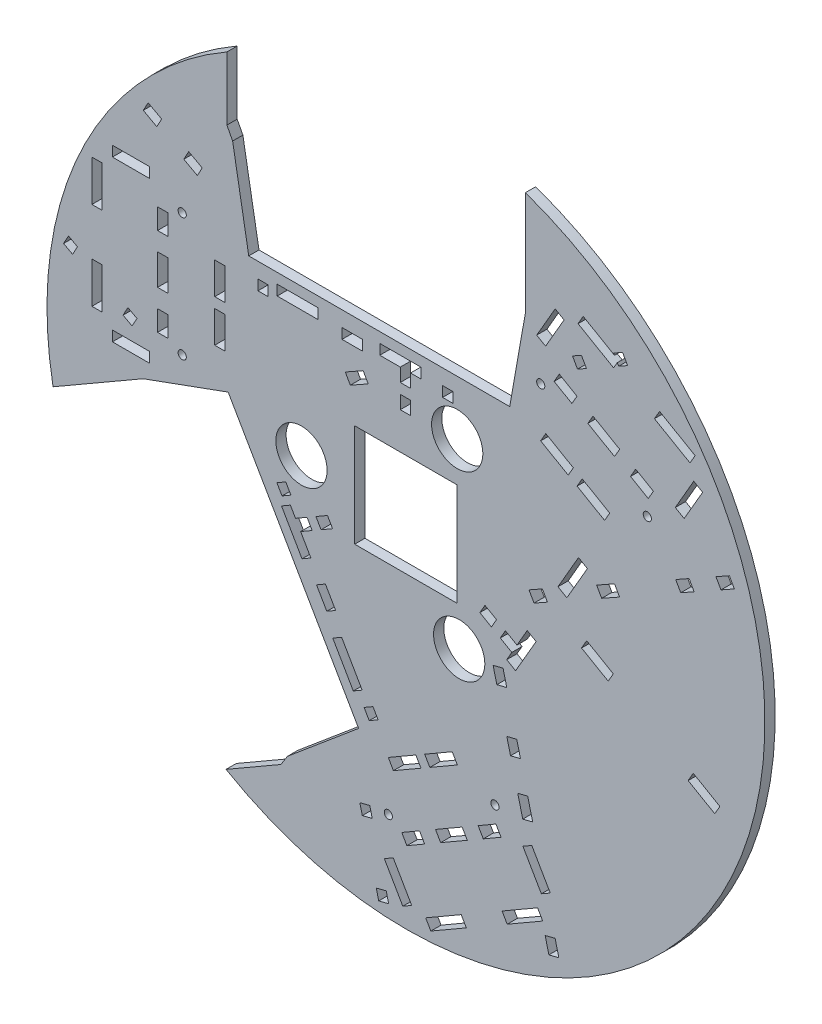
SolidWorks part; units mm, degrees
material "Balsa"
ref_plane "Plan de face" through (0, 0, 0) normal (0, 0, 1) x (1, 0, 0)
ref_plane "Plan de dessus" through (0, 0, 0) normal (0, 1, 0) x (1, 0, 0)
ref_plane "Plan de droite" through (0, 0, 0) normal (1, 0, 0) x (0, 0, -1)
sketch "Esquisse1" plane through (0, 0, 0) normal (0, 0, 1) x (1, 0, 0)
  circle A0 centre (148.0804, -12.1102) radius 175
  dimension "D1" = 350
extrude "Boss.-Extru.1" add sketch "Esquisse1" along normal blind 5
sketch "Esquisse2" plane through (0, 0, 5) normal (0, 0, 1) x (1, 0, 0)
  line L0 (135.3118, 53.7774) -> (135.3118, 48.7774)
  line L1 (5, 72.2774) -> (23, 72.2774)
  line L2 (5, 72.2774) -> (5, 67.2774)
  line L3 (5, 67.2774) -> (23, 67.2774)
  line L4 (23, 72.2774) -> (23, 67.2774)
  line L5 (-5, 62.2774) -> (0, 62.2774)
  line L6 (-5, 62.2774) -> (-5, 42.2774)
  line L7 (-5, 42.2774) -> (0, 42.2774)
  line L8 (0, 62.2774) -> (0, 42.2774)
  line L9 (-5, 19.2774) -> (0, 19.2774)
  line L10 (-5, 19.2774) -> (-5, -0.7226)
  line L11 (-5, -0.7226) -> (0, -0.7226)
  line L12 (0, 19.2774) -> (0, -0.7226)
  line L13 (5, -5.7226) -> (23, -5.7226)
  line L14 (5, -5.7226) -> (5, -10.7226)
  line L15 (5, -10.7226) -> (23, -10.7226)
  line L16 (23, -5.7226) -> (23, -10.7226)
  line L17 (27, 14.2774) -> (32, 14.2774)
  line L18 (27, 14.2774) -> (27, 4.2774)
  line L19 (27, 4.2774) -> (32, 4.2774)
  line L20 (32, 14.2774) -> (32, 4.2774)
  line L21 (27, 38.2774) -> (32, 38.2774)
  line L22 (27, 38.2774) -> (27, 23.2774)
  line L23 (27, 23.2774) -> (32, 23.2774)
  line L24 (32, 38.2774) -> (32, 23.2774)
  line L25 (27, 57.2774) -> (32, 57.2774)
  line L26 (27, 57.2774) -> (27, 47.2774)
  line L27 (27, 47.2774) -> (32, 47.2774)
  line L28 (32, 57.2774) -> (32, 47.2774)
  line L29 (54.86, 48.7774) -> (59.86, 48.7774)
  line L30 (54.86, 48.7774) -> (54.86, 33.2774)
  line L31 (54.86, 33.2774) -> (59.86, 33.2774)
  line L32 (59.86, 48.7774) -> (59.86, 33.2774)
  line L33 (54.86, 28.2774) -> (59.86, 28.2774)
  line L34 (54.86, 28.2774) -> (54.86, 12.7774)
  line L35 (54.86, 12.7774) -> (59.86, 12.7774)
  line L36 (59.86, 28.2774) -> (59.86, 12.7774)
  line L37 (85.3118, 53.7774) -> (105.3118, 53.7774)
  line L38 (85.3118, 53.7774) -> (85.3118, 48.7774)
  line L39 (85.3118, 48.7774) -> (105.3118, 48.7774)
  line L40 (105.3118, 53.7774) -> (105.3118, 48.7774)
  line L41 (145.3118, 37.2774) -> (150.3118, 37.2774)
  line L42 (145.3118, 37.2774) -> (145.3118, 30.7774)
  line L43 (145.3118, 30.7774) -> (150.3118, 30.7774)
  line L44 (150.3118, 37.2774) -> (150.3118, 30.7774)
  line L45 (135.3118, 48.7774) -> (145.3118, 48.7774)
  line L46 (155.3118, 48.7774) -> (135.3118, 48.7774) construction
  line L47 (145.3118, 48.7774) -> (145.3118, 42.2774)
  line L48 (145.3118, 42.2774) -> (150.3118, 42.2774)
  line L49 (150.3118, 42.2774) -> (150.3118, 48.7774)
  line L50 (150.3118, 48.7774) -> (155.3118, 48.7774)
  line L51 (155.3118, 48.7774) -> (155.3118, 53.7774)
  line L52 (155.3118, 53.7774) -> (135.3118, 53.7774)
  line L53 (292.7025, 69.6073) -> (283.7025, 54.0188)
  line L54 (292.7025, 69.6073) -> (288.3723, 72.1073)
  line L55 (288.3723, 72.1073) -> (279.3723, 56.5188)
  line L56 (283.7025, 54.0188) -> (279.3723, 56.5188)
  line L57 (289.0422, 83.2676) -> (286.5422, 78.9374)
  line L58 (289.0422, 83.2676) -> (271.7217, 93.2676)
  line L59 (271.7217, 93.2676) -> (269.2217, 88.9374)
  line L60 (286.5422, 78.9374) -> (269.2217, 88.9374)
  line L61 (251.8031, 104.7676) -> (249.3031, 100.4374)
  line L62 (251.8031, 104.7676) -> (234.4826, 114.7676)
  line L63 (234.4826, 114.7676) -> (231.9826, 110.4374)
  line L64 (249.3031, 100.4374) -> (231.9826, 110.4374)
  line L65 (225.1525, 108.6073) -> (216.1525, 93.0188)
  line L66 (225.1525, 108.6073) -> (220.8223, 111.1073)
  line L67 (220.8223, 111.1073) -> (211.8223, 95.5188)
  line L68 (216.1525, 93.0188) -> (211.8223, 95.5188)
  line L69 (231.473, 79.5547) -> (228.973, 75.2246)
  line L70 (231.473, 79.5547) -> (222.8127, 84.5547)
  line L71 (222.8127, 84.5547) -> (220.3127, 80.2246)
  line L72 (228.973, 75.2246) -> (220.3127, 80.2246)
  line L73 (252.2576, 67.5547) -> (249.7576, 63.2246)
  line L74 (252.2576, 67.5547) -> (239.2672, 75.0547)
  line L75 (239.2672, 75.0547) -> (236.7672, 70.7246)
  line L76 (249.7576, 63.2246) -> (236.7672, 70.7246)
  line L77 (268.7121, 58.0547) -> (266.2121, 53.7246)
  line L78 (268.7121, 58.0547) -> (260.0518, 63.0547)
  line L79 (260.0518, 63.0547) -> (257.5518, 58.7246)
  line L80 (266.2121, 53.7246) -> (257.5518, 58.7246)
  line L81 (247.4209, 38.1773) -> (244.9209, 33.8472)
  line L82 (247.4209, 38.1773) -> (233.9975, 45.9273)
  line L83 (233.9975, 45.9273) -> (231.4975, 41.5972)
  line L84 (244.9209, 33.8472) -> (231.4975, 41.5972)
  line L85 (229.6673, 48.4273) -> (227.1673, 44.0972)
  line L86 (229.6673, 48.4273) -> (216.2439, 56.1773)
  line L87 (216.2439, 56.1773) -> (213.7439, 51.8472)
  line L88 (227.1673, 44.0972) -> (213.7439, 51.8472)
  line L89 (211.5251, -33.996) -> (207.195, -31.496)
  line L90 (236.5251, 9.3053) -> (226.5251, -8.0153)
  line L91 (236.5251, 9.3053) -> (232.195, 11.8053)
  line L92 (232.195, 11.8053) -> (222.195, -5.5153)
  line L93 (226.5251, -8.0153) -> (222.195, -5.5153)
  line L94 (192.2357, -34.4063) -> (189.7357, -38.7364)
  line L95 (192.2357, -34.4063) -> (186.6065, -31.1563)
  line L96 (186.6065, -31.1563) -> (184.1065, -35.4864)
  line L97 (189.7357, -38.7364) -> (184.1065, -35.4864)
  line L98 (207.195, -31.496) -> (202.195, -40.1563)
  line L99 (202.195, -40.1563) -> (196.5658, -36.9063)
  line L100 (196.5658, -36.9063) -> (194.0658, -41.2364)
  line L101 (194.0658, -41.2364) -> (199.695, -44.4864)
  line L102 (199.695, -44.4864) -> (197.195, -48.8165)
  line L103 (197.195, -48.8165) -> (201.5251, -51.3165)
  line L104 (201.5251, -51.3165) -> (211.5251, -33.996)
  line L105 (146.5388, -178.2153) -> (137.5388, -162.6268)
  line L106 (146.5388, -178.2153) -> (150.869, -175.7153)
  line L107 (150.869, -175.7153) -> (141.869, -160.1268)
  line L108 (137.5388, -162.6268) -> (141.869, -160.1268)
  line L109 (160.1991, -181.8755) -> (157.6991, -177.5454)
  line L110 (160.1991, -181.8755) -> (177.5196, -171.8755)
  line L111 (177.5196, -171.8755) -> (175.0196, -167.5454)
  line L112 (157.6991, -177.5454) -> (175.0196, -167.5454)
  line L113 (197.4382, -160.3755) -> (194.9382, -156.0454)
  line L114 (197.4382, -160.3755) -> (214.7587, -150.3755)
  line L115 (214.7587, -150.3755) -> (212.2587, -146.0454)
  line L116 (194.9382, -156.0454) -> (212.2587, -146.0454)
  line L117 (214.0888, -139.2153) -> (205.0888, -123.6268)
  line L118 (214.0888, -139.2153) -> (218.4189, -136.7153)
  line L119 (218.4189, -136.7153) -> (209.4189, -121.1268)
  line L120 (205.0888, -123.6268) -> (209.4189, -121.1268)
  line L121 (185.7683, -130.1627) -> (183.2683, -125.8326)
  line L122 (185.7683, -130.1627) -> (194.4286, -125.1627)
  line L123 (194.4286, -125.1627) -> (191.9286, -120.8326)
  line L124 (183.2683, -125.8326) -> (191.9286, -120.8326)
  line L125 (164.9837, -142.1627) -> (162.4837, -137.8326)
  line L126 (164.9837, -142.1627) -> (177.9741, -134.6627)
  line L127 (177.9741, -134.6627) -> (175.4741, -130.3326)
  line L128 (162.4837, -137.8326) -> (175.4741, -130.3326)
  line L129 (148.5292, -151.6627) -> (146.0292, -147.3326)
  line L130 (148.5292, -151.6627) -> (157.1895, -146.6627)
  line L131 (157.1895, -146.6627) -> (154.6895, -142.3326)
  line L132 (146.0292, -147.3326) -> (154.6895, -142.3326)
  line L133 (141.9604, -123.2852) -> (139.4604, -118.9551)
  line L134 (141.9604, -123.2852) -> (155.3838, -115.5352)
  line L135 (155.3838, -115.5352) -> (152.8838, -111.2051)
  line L136 (139.4604, -118.9551) -> (152.8838, -111.2051)
  line L137 (159.7139, -113.0352) -> (157.2139, -108.7051)
  line L138 (159.7139, -113.0352) -> (173.1373, -105.2852)
  line L139 (173.1373, -105.2852) -> (170.6373, -100.9551)
  line L140 (157.2139, -108.7051) -> (170.6373, -100.9551)
  line L141 (97.4044, -56.1119) -> (101.7345, -53.6119)
  line L142 (122.4044, -99.4132) -> (112.4044, -82.0927)
  line L143 (122.4044, -99.4132) -> (126.7345, -96.9132)
  line L144 (126.7345, -96.9132) -> (116.7345, -79.5927)
  line L145 (112.4044, -82.0927) -> (116.7345, -79.5927)
  line L146 (106.6938, -39.2017) -> (104.1938, -34.8716)
  line L147 (106.6938, -39.2017) -> (112.323, -35.9517)
  line L148 (112.323, -35.9517) -> (109.823, -31.6216)
  line L149 (104.1938, -34.8716) -> (109.823, -31.6216)
  line L150 (101.7345, -53.6119) -> (96.7345, -44.9517)
  line L151 (96.7345, -44.9517) -> (102.3637, -41.7017)
  line L152 (102.3637, -41.7017) -> (99.8637, -37.3716)
  line L153 (99.8637, -37.3716) -> (94.2345, -40.6216)
  line L154 (94.2345, -40.6216) -> (91.7345, -36.2914)
  line L155 (91.7345, -36.2914) -> (87.4044, -38.7914)
  line L156 (87.4044, -38.7914) -> (97.4044, -56.1119)
  line L157 (135.3118, 53.7774) -> (135.3118, 48.7774) construction
  line L158 (105.3118, 53.7774) -> (135.3118, 53.7774) construction
  point P83 (148.0804, -12.1102)
  point P192 (148.0804, -12.1102)
  point P193 (148.0804, -12.1102)
  dimension "D1" = 3
extrude "Enlèv. mat.-Extru.1" cut sketch "Esquisse2" against normal blind 5
sketch "Esquisse6" plane through (0, 0, 5) normal (0, 0, 1) x (1, 0, 0)
  line L0 (93.9998, -7.2151) -> (100.2998, -18.127) construction
  line L1 (206.3213, 102.2219) -> (206.3213, 185.5637)
  line L2 (123.0804, -37.1102) -> (173.0804, -37.1102)
  line L3 (123.0804, -37.1102) -> (123.0804, 12.8898)
  line L4 (123.0804, 12.8898) -> (173.0804, 12.8898)
  line L5 (173.0804, -37.1102) -> (173.0804, 12.8898)
  line L6 (123.0804, -37.1102) -> (173.0804, 12.8898) construction
  line L7 (123.0804, 12.8898) -> (173.0804, -37.1102) construction
  line L8 (206.3213, 185.5637) -> (60.7972, 185.5637)
  line L9 (71.4438, 58.7774) -> (63.5848, 103.3483)
  line L10 (71.4438, 58.7774) -> (198.6608, 58.7774)
  line L11 (198.6608, 58.7774) -> (206.3213, 102.2219)
  line L12 (60.7972, 185.5637) -> (60.7972, 108.6824)
  line L13 (19.9456, -18.8381) -> (-52.2306, -60.5091)
  line L14 (-52.2306, -60.5091) -> (20.5314, -186.5366)
  line L15 (63.5848, 103.3483) -> (60.7972, 108.6824)
  line L16 (125.0083, -113.9232) -> (90.3383, -143.0148)
  line L17 (125.0083, -113.9232) -> (61.3998, -3.7501)
  line L18 (61.3998, -3.7501) -> (19.9456, -18.8381)
  line L20 (236.1714, -21.3074) -> (249.1617, -28.8074)
  line L21 (236.1714, -21.3074) -> (233.6714, -25.6375)
  line L22 (249.1617, -28.8074) -> (246.6617, -33.1375)
  line L23 (233.6714, -25.6375) -> (246.6617, -33.1375)
  line L24 (288.1329, -51.3074) -> (301.1233, -58.8074)
  line L25 (288.1329, -51.3074) -> (285.6329, -55.6375)
  line L26 (301.1233, -58.8074) -> (298.6233, -63.1375)
  line L27 (285.6329, -55.6375) -> (298.6233, -63.1375)
  line L28 (226.5251, -8.0153) -> (236.5251, 9.3053) construction
  line L29 (279.3723, 56.5188) -> (283.7025, 54.0188) construction
  line L31 (64.5427, 103.6743) -> (63.0102, 106.6067) construction
  line L32 (20.5314, -186.5366) -> (87.1126, -148.0959)
  line L33 (90.3383, -143.0148) -> (87.1126, -148.0959)
  circle A0 centre (173.06, 32.2774) radius 12.5
  circle A1 centre (174.0314, -55.9369) radius 12.5
  circle A2 centre (97.1498, -12.671) radius 12.5
  point P2 (148.0804, -12.1102)
  point P8 (148.0804, -12.1102)
  point P10 (148.0804, -12.1102)
  point P35 (148.0804, -12.1102)
  point P48 (148.0804, -12.1102)
  dimension "D12" = 25
  dimension "D3" = 50
  dimension "D4" = 50
  dimension "D5" = 70.8876
  dimension "D6" = 50.5804
  dimension "D7" = 127.217
  dimension "D8" = 100
  dimension "D9" = 100
  dimension "D10" = 145.5241
  dimension "D11" = 43.4444
  dimension "D13" = 5
  dimension "D14" = 15
  dimension "D15" = 15
  dimension "D16" = 45
  dimension "D17" = 15
  dimension "D18" = 89
  dimension "D19" = 2
  dimension "D20" = 1
  dimension "D1" = 3
extrude "Enlèv. mat.-Extru.6" cut sketch "Esquisse6" against normal blind 5
hole_wizard "Trous de centrage Ø4.0mm1" positions "Esquisse7" profile "Esquisse8" hole size "Ø4.0" standard "Ansi Metric" end condition through all
sketch "Esquisse7" plane through (148.0804, -12.1102, -78) normal (0, 0, -1) x (1, 0, 0)
  point P0 (65.7012, -88.0226)
  point P3 (117.6627, -58.0226)
  point P6 (-109.0804, -72.8876)
  point P9 (-109.0804, -12.8876)
  point P12 (-8.5823, 130.9102)
  point P15 (43.3792, 100.9102)
sketch "Esquisse8" plane through (213.7816, 75.9124, -78) normal (1, 0, 0) x (0, 1, 0)
  line L0 (0, 0) -> (0, 83)
  line L1 (0, 83) -> (2, 83)
  line L2 (2, 83) -> (2, 0)
  line L3 (2, 0) -> (0, 0)
  line L4 (0, -6.35) -> (0, 107.95) construction
  dimension "Diamètre du perçage jusqu'au prochain" = 4
  dimension "Profondeur du perçage jusqu'au prochain" = 83
sketch "Esquisse9" plane through (0, 0, 5) normal (0, 0, 1) x (1, 0, 0)
  line L0 (301.6473, 32.8747) -> (299.2005, 37.2351)
  line L1 (301.6473, 32.8747) -> (308.1879, 36.5449)
  line L2 (299.2005, 37.2351) -> (305.7411, 40.9053)
  line L3 (308.1879, 36.5449) -> (305.7411, 40.9053)
  line L4 (282.0254, 21.8642) -> (279.5786, 26.2246)
  line L5 (282.0254, 21.8642) -> (288.566, 25.5344)
  line L6 (279.5786, 26.2246) -> (286.1192, 29.8948)
  line L7 (288.566, 25.5344) -> (286.1192, 29.8948)
  line L8 (252.2089, 5.133) -> (249.7621, 9.4935)
  line L9 (252.2089, 5.133) -> (243.488, 0.2395)
  line L10 (249.7621, 9.4935) -> (241.0412, 4.5999)
  line L11 (243.488, 0.2395) -> (241.0412, 4.5999)
  line L12 (214.6084, -10.2326) -> (217.0552, -14.593)
  line L13 (214.6084, -10.2326) -> (208.0678, -13.9027)
  line L14 (217.0552, -14.593) -> (210.5146, -18.2632)
  line L15 (208.0678, -13.9027) -> (210.5146, -18.2632)
  line L16 (217.0552, -14.593) -> (243.488, 0.2395) construction
  line L17 (214.6084, -10.2326) -> (217.0552, -14.593) construction
  line L18 (256.1275, 104.7997) -> (251.7671, 102.3529)
  line L19 (256.1275, 104.7997) -> (253.6807, 109.1601)
  line L20 (251.7671, 102.3529) -> (249.3203, 106.7133)
  line L21 (253.6807, 109.1601) -> (249.3203, 106.7133)
  line L22 (236.0696, 93.5445) -> (231.7091, 91.0977)
  line L23 (236.0696, 93.5445) -> (233.6228, 97.9049)
  line L24 (231.7091, 91.0977) -> (229.2624, 95.4581)
  line L25 (233.6228, 97.9049) -> (229.2624, 95.4581)
  line L26 (129.6754, 33.8428) -> (120.9546, 28.9492)
  line L27 (129.6754, 33.8428) -> (127.2286, 38.2032)
  line L28 (120.9546, 28.9492) -> (118.5078, 33.3096)
  line L29 (127.2286, 38.2032) -> (118.5078, 33.3096)
  line L30 (256.1275, 104.7997) -> (120.9546, 28.9492) construction
  line L31 (301.6473, 32.8747) -> (217.0552, -14.593) construction
  line L32 (-16.4384, 23.2791) -> (-12.0459, 20.8904)
  line L33 (-16.4384, 23.2791) -> (-18.8272, 18.8866)
  line L34 (-12.0459, 20.8904) -> (-14.4347, 16.4979)
  line L35 (-18.8272, 18.8866) -> (-14.4347, 16.4979)
  line L36 (12.552, 7.5136) -> (16.9445, 5.1249)
  line L37 (12.552, 7.5136) -> (10.1633, 3.1211)
  line L38 (16.9445, 5.1249) -> (14.5558, 0.7324)
  line L39 (10.1633, 3.1211) -> (14.5558, 0.7324)
  line L42 (-26.9196, -12.1102) -> (148.0804, -12.1102) construction
  line L44 (22.4127, 98.9071) -> (29.0015, 95.324)
  line L45 (22.4127, 98.9071) -> (20.024, 94.5146)
  line L46 (29.0015, 95.324) -> (26.6128, 90.9315)
  line L47 (20.024, 94.5146) -> (26.6128, 90.9315)
  line L48 (42.179, 88.1579) -> (48.7677, 84.5748)
  line L49 (42.179, 88.1579) -> (39.7903, 83.7654)
  line L50 (48.7677, 84.5748) -> (46.379, 80.1823)
  line L51 (39.7903, 83.7654) -> (46.379, 80.1823)
  line L53 (148.0804, -12.1102) -> (9.6568, -109.2191) construction
  line L55 (129.7636, 187.6323) -> (148.0804, -12.1102) construction
  arc A0 (60.3638, -163.5394) -> (206.3213, 152.9141) centre (148.0804, -12.1102) ccw construction
  line B0 (154.106, -73.5915) -> (185.6214, -199.5155) construction
  line B1 (126.7996, -149.8343) -> (125.5857, -144.9839)
  line B2 (130.4361, -143.77) -> (125.5857, -144.9839)
  line B3 (131.65, -148.6204) -> (126.7996, -149.8343)
  line B4 (131.65, -148.6204) -> (130.4361, -143.77)
  line B5 (134.8115, -181.8469) -> (133.5976, -176.9965)
  line B6 (138.448, -175.7826) -> (133.5976, -176.9965)
  line B7 (139.6619, -180.633) -> (134.8115, -181.8469)
  line B8 (139.6619, -180.633) -> (138.448, -175.7826)
  line B9 (190.562, -54.5014) -> (195.4124, -53.2875)
  line B10 (197.2333, -60.5631) -> (195.4124, -53.2875)
  line B11 (192.3829, -61.777) -> (190.562, -54.5014)
  line B12 (192.3829, -61.777) -> (197.2333, -60.5631)
  line B13 (202.089, -79.9647) -> (197.2386, -81.1786)
  line B14 (199.0595, -88.4542) -> (197.2386, -81.1786)
  line B15 (203.9099, -87.2403) -> (202.089, -79.9647)
  line B16 (203.9099, -87.2403) -> (199.0595, -88.4542)
  line B17 (222.6043, -161.9364) -> (217.7539, -163.1503)
  line B18 (215.933, -155.8747) -> (217.7539, -163.1503)
  line B19 (220.7834, -154.6608) -> (222.6043, -161.9364)
  line B20 (220.7834, -154.6608) -> (215.933, -155.8747)
  dimension "D9" = 170.2546
  dimension "D1" = 10
  dimension "D2" = 5
  dimension "D3" = 7.5
  dimension "D4" = 10
  dimension "D5" = 7.5
  dimension "D6" = 7.5
  dimension "D7" = 5
  dimension "D8" = 117
  dimension "D10" = 167.3371
  dimension "D11" = 69
  dimension "D12" = 35.051
  dimension "D13" = 30.31
  dimension "D14" = 5
sketch_block_instance "Bloc1-1"
sketch_block "Bloc1"
extrude "Holes catchers of glass" cut sketch "Esquisse9" against normal blind 10
sketch "Esquisse10" plane through (0, 0, 5) normal (0, 0, 1) x (1, 0, 0)
  line L0 (89.4961, -27.6144) -> (91.9961, -31.9445)
  line L1 (89.4961, -27.6144) -> (85.1672, -30.1137)
  line L2 (91.9961, -31.9445) -> (87.6672, -34.4438)
  line L3 (85.1672, -30.1137) -> (87.6672, -34.4438)
  dimension "D1" = 4.9986
extrude "Holes boards servo" cut sketch "Esquisse10" against normal blind 10
sketch "Esquisse11" plane through (0, 0, 5) normal (0, 0, 1) x (1, 0, 0)
  line L0 (109.4829, -72.2325) -> (104.4829, -63.5722)
  line L1 (109.4829, -72.2325) -> (113.813, -69.7325)
  line L2 (104.4829, -63.5722) -> (108.813, -61.0722)
  line L3 (113.813, -69.7325) -> (108.813, -61.0722)
  line L4 (125.166, -99.3964) -> (108.8992, -71.2215) construction
  line L6 (116.7345, -79.5927) -> (112.4044, -82.0927) construction
  line L7 (130.166, -108.0567) -> (134.4961, -105.5567)
  line L8 (130.166, -108.0567) -> (127.666, -103.7266)
  line L9 (134.4961, -105.5567) -> (131.9961, -101.2266)
  line L10 (127.666, -103.7266) -> (131.9961, -101.2266)
  line L11 (207.4302, -101.3064) -> (209.8581, -111.0072)
  line L12 (170.9253, 51.2774) -> (165.9253, 51.2774)
  line L13 (170.9253, 51.2774) -> (170.9253, 46.2774)
  line L14 (170.9253, 46.2774) -> (165.9253, 46.2774)
  line L15 (165.9253, 51.2774) -> (165.9253, 46.2774)
  line L16 (126.9253, 51.2774) -> (116.9253, 51.2774)
  line L17 (126.9253, 51.2774) -> (126.9253, 46.2774)
  line L18 (126.9253, 46.2774) -> (116.9253, 46.2774)
  line L19 (116.9253, 51.2774) -> (116.9253, 46.2774)
  line L20 (80.9253, 51.2774) -> (75.9253, 51.2774)
  line L21 (80.9253, 51.2774) -> (80.9253, 46.2774)
  line L22 (80.9253, 46.2774) -> (75.9253, 46.2774)
  line L23 (75.9253, 51.2774) -> (75.9253, 46.2774)
  line L24 (207.4302, -101.3064) -> (202.5798, -102.5203)
  line L25 (209.8581, -111.0072) -> (205.0077, -112.2211)
  line L26 (202.5798, -102.5203) -> (205.0077, -112.2211)
  line L27 (203.9099, -87.2403) -> (202.089, -79.9647) construction
  line L28 (220.7834, -154.6608) -> (215.933, -155.8747) construction
  dimension "D1" = 10
  dimension "D2" = 10
  dimension "D3" = 5
  dimension "D4" = 5
  dimension "D5" = 5
  dimension "D6" = 10
  dimension "D7" = 45
extrude "Enlèv. mat.-Extru.7" cut sketch "Esquisse11" against normal blind 5
